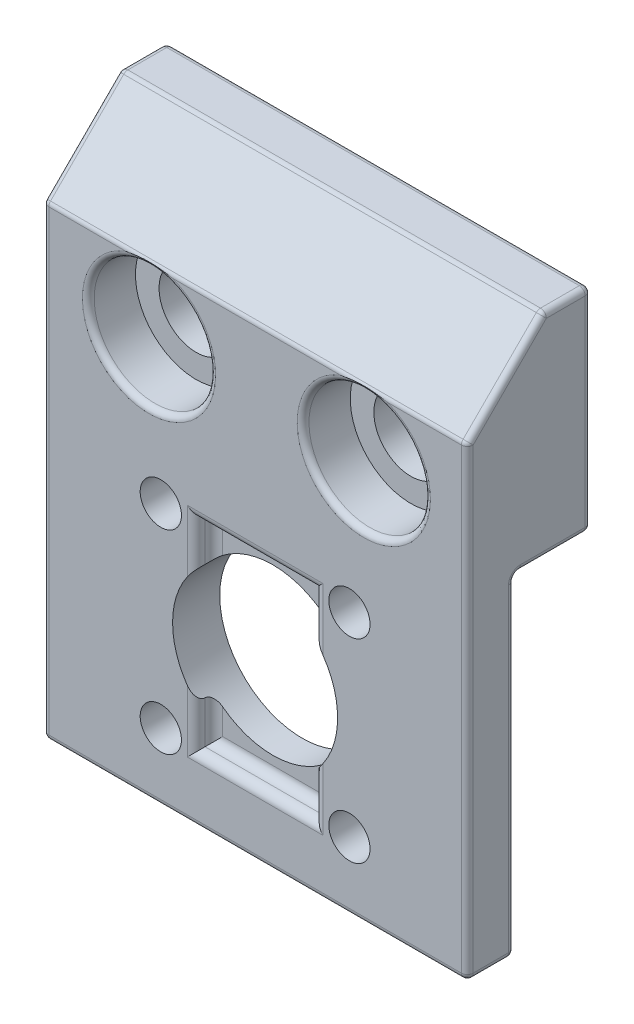
SolidWorks part; units mm, degrees
ref_plane "Front Plane" through (0, 0, 0) normal (0, 0, 1) x (1, 0, 0)
ref_plane "Top Plane" through (0, 0, 0) normal (0, 1, 0) x (1, 0, 0)
ref_plane "Right Plane" through (0, 0, 0) normal (1, 0, 0) x (0, 0, -1)
sketch "Sketch3" plane through (0, 0, 0) normal (0, 0, 1) x (1, 0, 0)
  line L0 (6.625, 0) -> (-6.625, 0) construction
  line L1 (-8, -8) -> (8, -8) construction
  line L2 (-8, -8) -> (-8, 8) construction
  line L3 (-8, 8) -> (8, 8) construction
  line L4 (0, 0) -> (0, 22.5) construction
  line L5 (-9, 22.5) -> (9, 22.5) construction
  line L12 (8, -8) -> (8, 8) construction
  line L13 (-8, -8) -> (8, 8) construction
  line L14 (-8, 8) -> (8, -8) construction
  line L15 (-5, -5.5) -> (-8.25, -5.5)
  line L16 (-5, -5.5) -> (-5, 5.5)
  line L17 (-5, 5.5) -> (-8.25, 5.5)
  line L18 (-8.25, -5.5) -> (-8.25, 5.5)
  line L19 (-5, -5.5) -> (-8.25, 5.5) construction
  line L20 (-5, 5.5) -> (-8.25, -5.5) construction
  line L21 (5, -5.5) -> (8.25, -5.5)
  line L22 (5, -5.5) -> (5, 5.5)
  line L23 (5, 5.5) -> (8.25, 5.5)
  line L24 (8.25, -5.5) -> (8.25, 5.5)
  line L25 (5, -5.5) -> (8.25, 5.5) construction
  line L26 (5, 5.5) -> (8.25, -5.5) construction
  circle A0 centre (8, 8) radius 1.75
  circle A1 centre (8, -8) radius 1.75
  circle A2 centre (-8, 8) radius 1.75
  circle A3 centre (-8, -8) radius 1.75
  circle A4 centre (0, 0) radius 14 construction
  circle A6 centre (-9, 22.5) radius 3.4
  circle A7 centre (9, 22.5) radius 3.4
  point P2 (0, 0)
  point P14 (-6.625, 0)
  point P19 (6.625, 0)
  point P27 (0, 0)
  dimension "D2" = 3.5
  dimension "D1" = 28
  dimension "D7" = 22.5
  dimension "D9" = 6.8
  dimension "D3" = 16
  dimension "D4" = 10
  dimension "D5" = 16.5
  dimension "D6" = 11
  dimension "D8" = 18
sketch "Sketch5" plane through (0, 0, 0) normal (1, 0, 0) x (0, 0, -1)
  line L0 (0, 14) -> (0, -14) construction
  line L1 (0, 14) -> (0, -14)
  line L2 (0, 14) -> (6.5, 14)
  line L3 (6.5, 14) -> (6.5, 32)
  line L4 (6.5, 32) -> (2.5, 32)
  line L7 (-4, 25.5) -> (-4, -14)
  line L8 (-4, -14) -> (0, -14)
  line L9 (-4, 25.5) -> (2.5, 32)
  line L10 (6.5, 20) -> (-4, 20) construction
  line L18 (-2.5, -5.0154) -> (-2.5, 5.0154) construction
  point P1 (6.5, 17.6832)
  point P2 (-5.4692, 22.5)
  point P9 (0, 0)
  point P30 (-2.5, 0)
  dimension "D1" = 1.5
  dimension "D2" = 6
  dimension "D3" = 4
  dimension "D4" = 18
  dimension "D5" = 45
  dimension "D6" = 9
extrude "Boss-Extrude1" add sketch "Sketch5" along normal mid plane 36 contours L7 L8 L1 L2 L3 L4 | L9 region at (0, 0, 0.4718)
sketch "Sketch6" plane through (0, 0, 0) normal (0, 0, -1) x (-1, 0, 0)
  line L1 (-5, -8.5) -> (5, -8.5)
  line L2 (-5, -8.5) -> (-5, 8.5)
  line L3 (-5, 8.5) -> (5, 8.5)
  line L4 (18, -14) -> (18, 14)
  line L5 (18, 14) -> (-18, 14)
  line L6 (-18, 14) -> (-18, -14)
  line L7 (-18, -14) -> (18, -14)
  line L8 (18, -14) -> (18, 14)
  line L9 (18, 14) -> (-18, 14)
  line L10 (-18, 14) -> (-18, -14)
  line L11 (-18, -14) -> (18, -14)
  line L12 (5, -8.5) -> (5, 8.5)
  line L13 (-5, -8.5) -> (5, 8.5) construction
  line L14 (-5, 8.5) -> (5, -8.5) construction
  line L15 (-8, -8.25) -> (8, -8.25) construction
  line L16 (-8, -8.25) -> (-8, 8.25) construction
  line L17 (-8, 8.25) -> (8, 8.25) construction
  line L18 (8, -8.25) -> (8, 8.25) construction
  line L19 (-8, -8.25) -> (8, 8.25) construction
  line L20 (-8, 8.25) -> (8, -8.25) construction
  line L21 (-9, 20) -> (9, 20)
  circle A0 centre (0, 0) radius 7
  point P16 (0, 20)
  point P20 (0, 20)
  dimension "D2" = 14
  dimension "D3" = 10
  dimension "D4" = 17
  dimension "D5" = 16
  dimension "D6" = 16.5
  dimension "D7" = 18
  dimension "D1" = 0
extrude "Cut-Extrude1" cut sketch "Sketch6" against normal blind 10 contours L12 A0 L2 | L12 A0 | L2 A0 region at (5.8107, 0, 0) region at (0, 0, 0) region at (-5.8107, 0, 0)
extrude "Cut-Extrude2" cut sketch "Sketch6<4>" along normal up to vertex (-2.5 mm away) from surface contours A0 L12 L3 L2 | A0 L2 L1 L12 region at (0, -7.3379, 0) region at (0, 7.3379, 0) up to point (0, 0, 2.5) starting at face at (0, 7, 4)
sketch "Sketch6<4>" plane through (0, 0, 0) normal (0, 0, -1) x (-1, 0, 0) same geometry as "Sketch6"
sketch "Sketch8" plane through (0, 0, 4) normal (0, 0, 1) x (1, 0, 0)
  point P0 (8, 8.25)
  point P2 (8, -8.25)
  point P4 (-8, -8.25)
  point P6 (-8, 8.25)
hole_wizard "Ø4.0mm Dowel Hole1" positions "Sketch8" profile "Sketch9" hole size "Ø4.0" standard "ANSI Metric" end condition through all
sketch "Sketch9" plane through (8, 8.25, 4) normal (1, 0, 0) x (0, -1, 0)
  line L0 (0, 0) -> (0, 10.5)
  line L1 (0, 10.5) -> (1.75, 10.5)
  line L2 (1.75, 10.5) -> (1.75, 0)
  line L5 (1.75, 0) -> (0, 0)
  line L11 (0, -6.35) -> (0, 107.95) construction
  dimension "Thru Hole Dia." = 3.5
  dimension "Thru Hole Depth" = 10.5
sketch "Sketch11" plane through (0, 0, 4) normal (0, 0, 1) x (1, 0, 0)
  line L0 (9, 20) -> (-9, 20) construction
  line L1 (9, 20) -> (-9, 20)
  point P1 (-9, 20)
  point P4 (9.2211, 20)
hole_wizard "CBORE for M5 Hex Head Bolt1" positions "Sketch11" profile "Sketch12" counterbore size "M5" standard "ANSI Metric" end condition through all
sketch "Sketch12" plane through (9.2211, 20, 4) normal (1, 0, 0) x (0, -1, 0)
  line L0 (0, 0) -> (0, 10.5)
  line L1 (0, 10.5) -> (3.15, 10.5)
  line L3 (3.15, 10.5) -> (3.15, 4)
  line L4 (3.15, 4) -> (5.15, 4)
  line L5 (5.15, 4) -> (5.15, 0)
  line L7 (5.15, 0) -> (0, 0)
  line L11 (0, -6.35) -> (0, 107.95) construction
  dimension "Thru Hole Dia." = 6.3
  dimension "Thru Hole Depth" = 10.5
  dimension "C'Bore Dia." = 10.3
  dimension "C'Bore Depth" = 4
fillet "Fillet1" radius 0.5 23 edges at (-3.85, 20, 4) (14.3711, 20, 4) (-18, -14, 2) (-18, 0, 0) (-18, 14, -3.25) (0, 14, 0) (0, 14, -6.5) (-18, 23, -6.5) (-18, 5.75, 4) (-18, 28.75, 0.75) (-18, 32, -4.5) (0, 25.5, 4) (0, 32, -6.5) (0, 32, -2.5) (18, 32, -4.5) (18, 28.75, 0.75) (18, 23, -6.5) (18, 14, -3.25) (0, -14, 0) (18, 0, 0) (18, -14, 2) (0, -14, 4) (18, 5.75, 4)
fillet "Fillet3" radius 0.75 12 edges at (5, -6.6995, 4) (5, -6.6995, 2.5) (0, -8.5, 2.5) (5, 6.6995, 4) (5, 6.6995, 2.5) (-5, 6.6995, 4) (0, 8.5, 4) (0, 8.5, 2.5) (-5, 6.6995, 2.5) (0, -8.5, 4) (-5, -6.6995, 4) (-5, -6.6995, 2.5)
